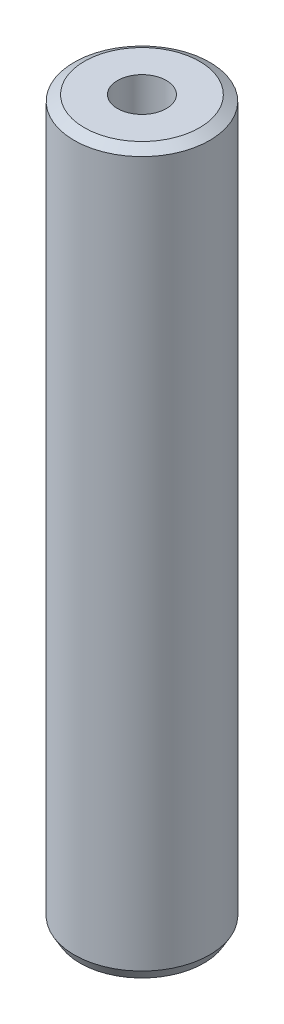
SolidWorks part; units mm, degrees
ref_plane "Front Plane" through (0, 0, 0) normal (0, 0, 1) x (1, 0, 0)
ref_plane "Top Plane" through (0, 0, 0) normal (0, 1, 0) x (1, 0, 0)
ref_plane "Right Plane" through (0, 0, 0) normal (1, 0, 0) x (0, 0, -1)
sketch "Sketch1" plane through (0, 0, 0) normal (0, 1, 0) x (1, 0, 0)
  circle A0 centre (0, 0) radius 40
  dimension "SHAFT_OD" = 80
extrude "Boss-Extrude1" add sketch "Sketch1" along normal blind 425.8717
sketch "Sketch2" plane through (0, 0, 0) normal (0, 1, 0) x (1, 0, 0)
  circle A0 centre (0, 0) radius 14.4083
  dimension "BORE_D" = 28.8167
extrude "Cut-Extrude1" cut sketch "Sketch2" along normal through all
chamfer "Chamfer1" distance 3.4707 angle 60 2 edges at (0, 425.8717, 40) (0, 0, 40) first distance on face at (0, 425.8717, 40) first distance on face at (0, 0, 14.4083)
